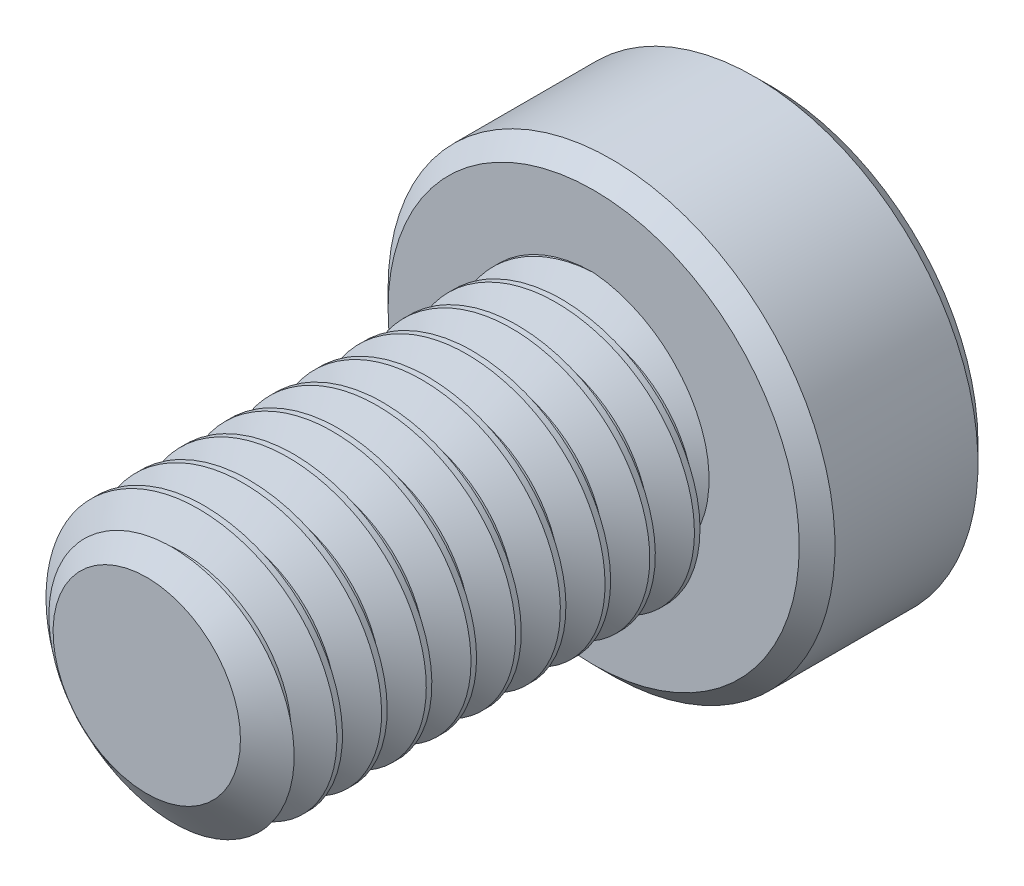
SolidWorks part; units mm, degrees
ref_plane "Front Plane" through (0, 0, 0) normal (0, 0, 1) x (1, 0, 0)
ref_plane "Top Plane" through (0, 0, 0) normal (0, 1, 0) x (1, 0, 0)
ref_plane "Right Plane" through (0, 0, 0) normal (1, 0, 0) x (0, 0, -1)
sketch "Sketch1" plane through (0, 0, 0) normal (0, 0, 1) x (1, 0, 0)
  circle A0 centre (0, 0) radius 3
  dimension "OD" = 6
extrude "Extrude1" add sketch "Sketch1" against normal blind 10
sketch "Sketch2" plane through (0, 0, 0) normal (0, 0, 1) x (1, 0, 0)
  circle A0 centre (0, 0) radius 3 construction
  circle A1 centre (0, 0) radius 3
curve "Helix/Spiral1" pitch 1 height 11 turns 11 parameters "pitch"=1
sketch "Sketch3" plane through (0, 0, 0) normal (1, 0, 0) x (0, 0, -1)
  line L0 (-0.875, 3) -> (-0.5, 2.3505)
  line L1 (-0.5, 2.3505) -> (-0.375, 2.3505)
  line L2 (-0.375, 2.3505) -> (0, 3)
  line L3 (-0.875, 3) -> (0, 3)
  line L4 (-0.4375, 3) -> (-0.4375, 2.3505) construction
  line L5 (-0.6875, 2.6752) -> (-0.1875, 2.6752) construction
  line L6 (0, 3) -> (0, -3) construction
  dimension "D1" = 0.125
  dimension "D2" = 0.5
  dimension "D3" = 60
sweep "Cut-Sweep1" cut profiles "Sketch3" path "Helix/Spiral1"
sketch "Sketch4" plane through (0, 0, 0) normal (1, 0, 0) x (0, 0, -1)
  line L0 (0.6327, 3) -> (0, 2.0965)
  line L1 (0, 2.0965) -> (0, 3)
  line L2 (0.6327, 3) -> (0, 3)
  line L3 (-0.875, 3) -> (0, 3) construction
  line L4 (0, 0) -> (7.0209, 0) construction
  dimension "D1" = 55
  dimension "D2" = 0.254
revolve "Cut-Revolve1" cut sketch "Sketch4" angle 360 about L4
sketch "Sketch6" plane through (0, 0, -10) normal (0, 0, -1) x (-1, 0, 0)
  circle A0 centre (0, 0) radius 5
  dimension "head dia" = 10
extrude "Extrude2" add sketch "Sketch6" along normal blind 4
sketch "Sketch5" plane through (0, 0, 0) normal (1, 0, 0) x (0, 0, -1)
  line L1 (10, 3) -> (14.1202, 3)
  line L2 (10, 3) -> (10, 0)
  line L3 (10, 0) -> (14, 0)
  line L4 (14, 2.6698) -> (14, 0)
  line L5 (14.1202, 3) -> (14, 2.6698)
  line L6 (0, 0) -> (9.9695, 0) construction
  line L7 (10, 5) -> (10, -5) construction
  point P3 (14, 3)
  point P10 (14, 3)
  dimension "D1" = 0.3302
  dimension "Thread min" = 14
  dimension "D2" = 3
  dimension "D3" = 20
revolve "partially thread" [suppressed] add sketch "Sketch5" angle 360 about L6
sketch "Sketch7" plane through (0, 0, -14) normal (0, 0, -1) x (-1, 0, 0)
  line L1 (0, 2.3094) -> (-2, 1.1547)
  line L2 (-2, 1.1547) -> (-2, -1.1547)
  line L3 (-2, -1.1547) -> (0, -2.3094)
  line L4 (0, -2.3094) -> (2, -1.1547)
  line L5 (2, -1.1547) -> (2, 1.1547)
  line L6 (2, 1.1547) -> (0, 2.3094)
  circle A0 centre (0, 0) radius 2 construction
  dimension "hex dia" = 4
extrude "Cut-Extrude1" cut sketch "Sketch7" against normal blind 3
sketch "Sketch8" plane through (0, 0, -14) normal (0, 0, -1) x (-1, 0, 0)
  circle A0 centre (0, 0) radius 2.3094
extrude "Cut-Extrude2" cut sketch "Sketch8" against normal through all draft 45
chamfer "Chamfer1" distance 0.4 angle 45 2 edges at (-5, 0, -14) (-5, 0, -10)
sketch "Sketch9" plane through (0, 0, 0) normal (1, 0, 0) x (0, 0, -1)
  line L0 (0, 3) -> (0, -3) construction
  line L1 (5.5, 3) -> (5.5, -3) construction
  dimension "D1" = 5.5
equation "\"D3@Helix/Spiral1\" = \"screw length@Extrude1\"+\"pitch@Helix/Spiral1\""
equation "\"D1@Sketch3\" = \"pitch@Helix/Spiral1\"*.125"
equation "\"D2@Sketch3\" = \"pitch@Helix/Spiral1\"*.5"
equation "\"D1@Cut-Extrude1\" = \"hex dia@Sketch7\"*.75"
equation "\"D1@Chamfer1\" = \"head depth@Extrude2\"*.1"
equation "\"D1@Sketch9\" = \"pitch@Helix/Spiral1\"*5.5"
equation "\"D2@Sketch5\" = \"OD@Sketch1\"/2"
